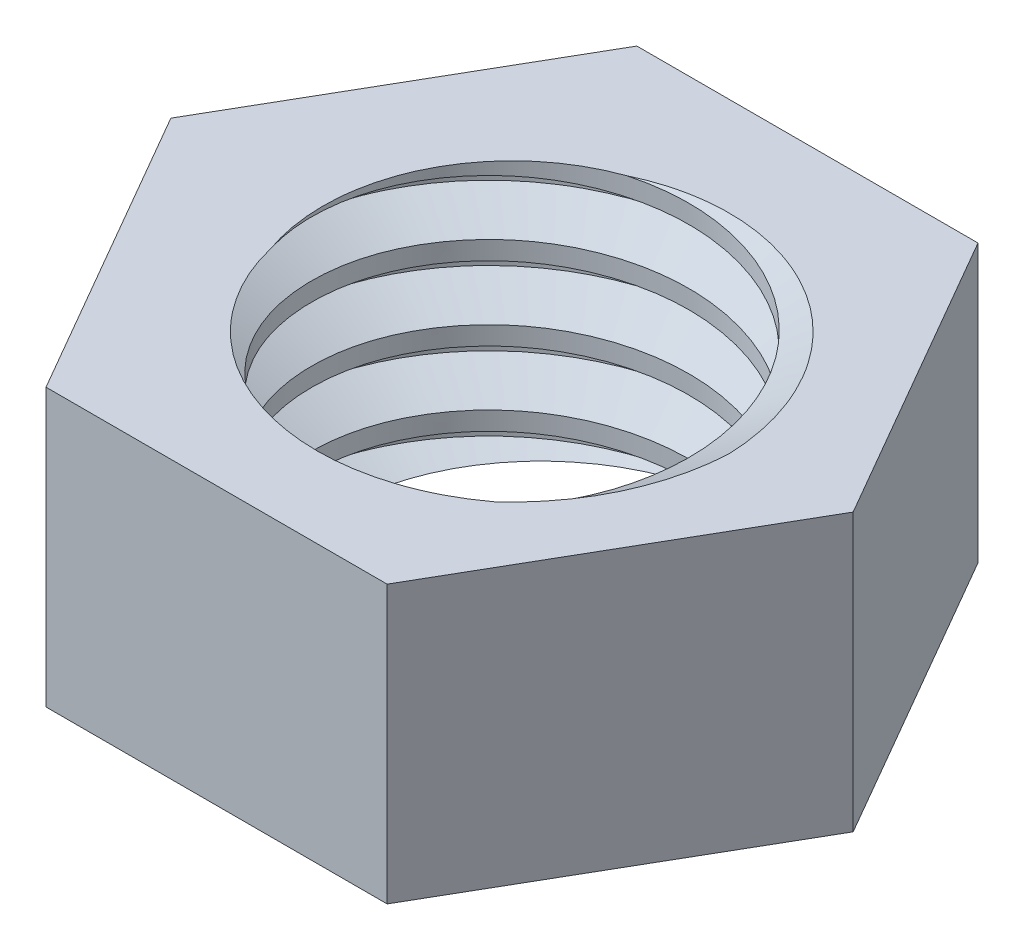
SolidWorks part; units mm, degrees
ref_plane "Front Plane" through (0, 0, 0) normal (0, 0, 1) x (1, 0, 0)
ref_plane "Top Plane" through (0, 0, 0) normal (0, 1, 0) x (1, 0, 0)
ref_plane "Right Plane" through (0, 0, 0) normal (1, 0, 0) x (0, 0, -1)
sketch "Sketch1" plane through (0, 0, 0) normal (0, 1, 0) x (1, 0, 0)
  line L0 (-90.4875, 0) -> (0, 0) construction
  line L14 (5.8659, 10.16) -> (-5.8659, 10.16)
  line L15 (-5.8659, 10.16) -> (-11.7318, 0)
  line L16 (-11.7318, 0) -> (-5.8659, -10.16)
  line L17 (-5.8659, -10.16) -> (5.8659, -10.16)
  line L18 (5.8659, -10.16) -> (11.7318, 0)
  line L19 (11.7318, 0) -> (5.8659, 10.16)
  circle A3 centre (0, 0) radius 7.875
  circle A6 centre (0, 0) radius 10.16 construction
  point P0 (0, 0)
  dimension "D2" = 15.75
  dimension "D11" = 10.16
extrude "Boss-Extrude1" add sketch "Sketch1" along normal blind 9.525 contours A3 region at (8.53, 0, -4.9248)
thread "Thread1" pitch 2.54 method extrude profile "Thread Profile1" start angle 3, offset 3.81, length 15.08, pitch 2.54, diameter 15.75
ref_plane "Plane1" through (-7.8642, 13.335, -0.4121) normal (-0.0523, 0, 0.9986) x (-0.9986, 0, -0.0523)
sketch "Thread Profile1" plane through (-7.8642, 13.335, -0.4121) normal (-0.0523, 0, 0.9986) x (-0.9986, 0, -0.0523)
  line L0 (0, 0) -> (0, 2.54) construction
  line L11 (0, 0) -> (0, 2.2225)
  line L12 (0, 2.2225) -> (-1.3748, 1.4287)
  line L13 (-1.3748, 1.4287) -> (-1.3748, 0.7937)
  line L15 (-1.3748, 0.7937) -> (0, 0)
  line L17 (-1.3748, 1.1112) -> (0, 1.1112) construction
  point P2 (0, 0)
  dimension "Pitch" = 2.54
  dimension "Profile_Angle" = 60
  dimension "Profile_Land" = 0.635
  dimension "Profile_Height" = 1.3748
sketch "Sketch25" plane through (8.7988, 0, -5.08) normal (0.866, 0, -0.5) x (-0.5, 0, -0.866)
  line L0 (-5.8659, 9.525) -> (5.8659, 9.525) construction
  line L1 (-9.3289, 9.525) -> (8.9735, 9.525)
  line L2 (-5.8659, 0) -> (5.8659, 0) construction
  line L3 (-9.0623, 0) -> (8.9291, 0)
  line L4 (-9.0623, 0) -> (-9.0623, -5.0697)
  line L5 (-9.0623, -5.0697) -> (8.9291, -5.0697)
  line L6 (8.9291, -5.0697) -> (8.9291, 0)
  line L7 (-9.3289, 9.525) -> (-9.3289, 16.5179)
  line L8 (-9.3289, 16.5179) -> (8.9735, 16.5179)
  line L9 (8.9735, 16.5179) -> (8.9735, 9.525)
extrude "Cut-Extrude1" cut sketch "Sketch25" against normal through all
